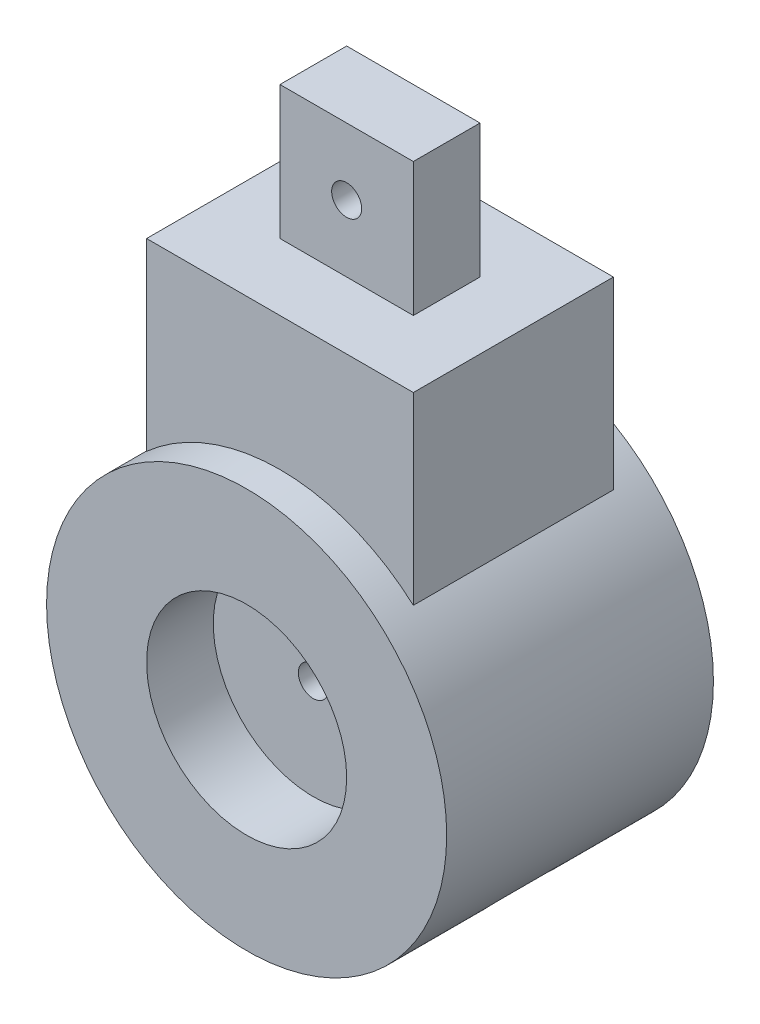
SolidWorks part; units mm, degrees
material "Rubber"
ref_plane "Front Plane" through (0, 0, 0) normal (0, 0, 1) x (1, 0, 0)
ref_plane "Top Plane" through (0, 0, 0) normal (0, 1, 0) x (1, 0, 0)
ref_plane "Right Plane" through (0, 0, 0) normal (1, 0, 0) x (0, 0, -1)
sketch "Sketch8" plane through (0, 0, 0) normal (0, 0, 1) x (1, 0, 0)
  line L5 (0, 0) -> (40, 0)
  line L6 (0, 0) -> (0, -50)
  line L7 (0, -50) -> (40, -50)
  line L8 (40, 0) -> (40, -50)
  dimension "D1" = 40
  dimension "D2" = 50
extrude "Boss-Extrude7" add sketch "Sketch8" along normal mid plane 30
sketch "Sketch11" plane through (0, 0, 0) normal (0, 0, 1) x (1, 0, 0)
  line L1 (0, -50) -> (40, -50) construction
  circle A1 centre (20, -50) radius 30
  dimension "D1" = 60
extrude "Boss-Extrude8" add sketch "Sketch11" along normal mid plane 40
ref_plane "Plane2" through (0, 0, 0) normal (0, 0, -1) x (-1, 0, 0)
sketch "Sketch14" plane through (0, 0, 0) normal (0, 0, -1) x (-1, 0, 0)
  line L0 (-40, 0) -> (0, 0) construction
  line L1 (-30, 0) -> (-10, 0)
  line L2 (-30, 0) -> (-30, 20)
  line L3 (-30, 20) -> (-10, 20)
  line L4 (-10, 0) -> (-10, 20)
  line L5 (0, 0) -> (-40, 0)
  dimension "D1" = 20
  dimension "D2" = 20
  dimension "D3" = 10
extrude "Boss-Extrude9" add sketch "Sketch14" along normal mid plane 10 contours L1 L4 L3 L2 region at (20, 10, 0)
sketch "Sketch15" plane through (0, 0, 0) normal (-1, 0, 0) x (0, 0, 1)
  line L10 (-20, -80) -> (20, -80) construction
  line L11 (-5, -30) -> (5, -30)
  line L13 (-5, -80) -> (5, -80)
  line L14 (5, -30) -> (5, -80)
  line L15 (-5, -30) -> (-5, -80)
  dimension "D1" = 50
extrude "Cut-Extrude6" cut sketch "Sketch15" along normal blind 15 and the other way blind 29
sketch "Sketch16" plane through (0, 0, 5) normal (0, 0, 1) x (1, 0, 0)
  line L0 (30, 0) -> (30, 20) construction
  line L1 (30, 20) -> (10, 20) construction
  circle A0 centre (20, 10) radius 2.25
  dimension "D1" = 4.5
  dimension "D2" = 10
  dimension "D3" = 10
extrude "Cut-Extrude7" cut sketch "Sketch16" against normal mid plane 125
sketch "Sketch17" plane through (0, 0, 20) normal (0, 0, 1) x (1, 0, 0)
  circle A0 centre (20, -50) radius 15
  dimension "D1" = 30
extrude "Cut-Extrude8" cut sketch "Sketch17" against normal blind 10
sketch "Sketch18" plane through (0, 0, 10) normal (0, 0, 1) x (1, 0, 0)
  circle A0 centre (20, -50) radius 2.25
  dimension "D1" = 4.5
extrude "Cut-Extrude9" cut sketch "Sketch18" against normal blind 31
mirror "Mirror3" about plane through (0, 0, 0) normal (0, 0, -1) of "Cut-Extrude8"
sketch "Sketch19" plane through (29, 0, 0) normal (-1, 0, 0) x (0, 0, 1)
  line L1 (-5, -30) -> (5, -30)
  line L2 (-5, -30) -> (-5, -80)
  line L3 (-5, -80) -> (5, -80)
  line L4 (5, -30) -> (5, -80)
extrude "Cut-Extrude10" cut sketch "Sketch19" against normal blind 41
sketch "Sketch20" plane through (0, 0, 5) normal (0, 0, -1) x (-1, 0, 0)
  line L0 (-30, -38.8197) -> (-40, -27.6393)
  line L1 (-31.1803, -60) -> (-42.3607, -70)
  arc A0 (-40, -27.6393) -> (-42.3607, -70) centre (-20, -50) ccw
  arc A1 (-30, -38.8197) -> (-31.1803, -60) centre (-20, -50) ccw
extrude "Boss-Extrude10" add sketch "Sketch20" along normal blind 10
